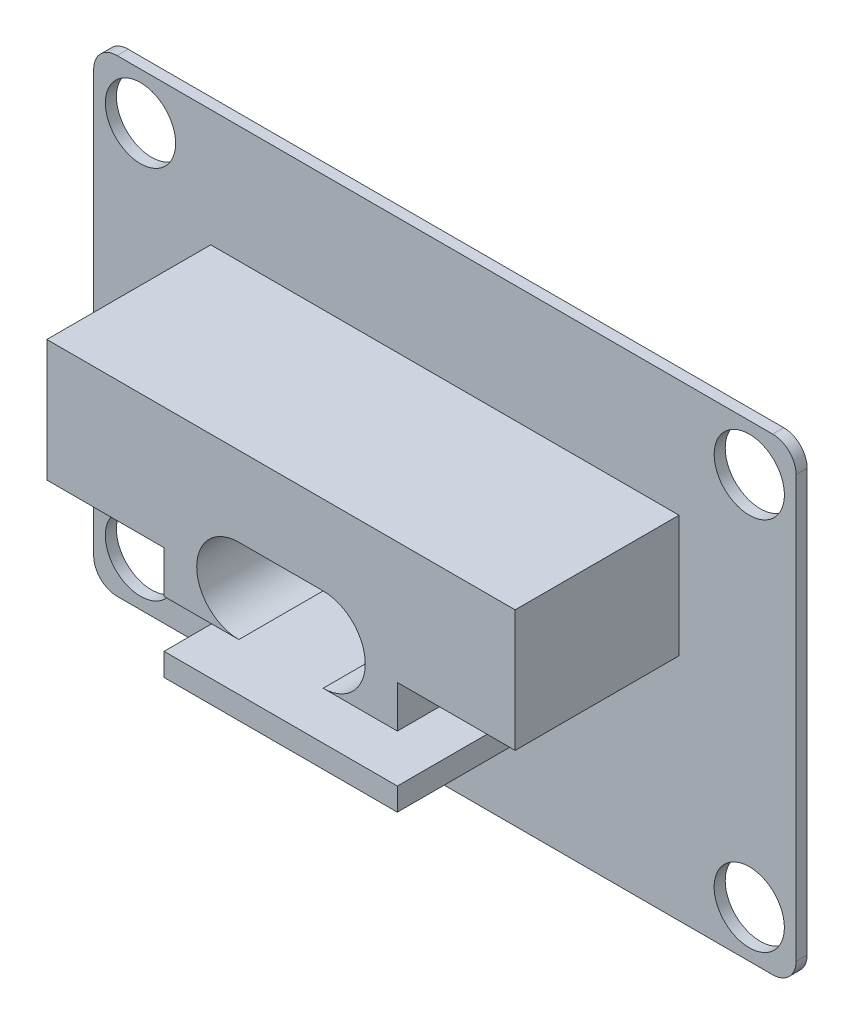
SolidWorks part; units mm, degrees
note: The reader was unsure of these and kept them because the rebuilt part matched: shared geometry of "Sketch3<3>".
ref_plane "Front Plane" through (0, 0, 0) normal (0, 0, 1) x (1, 0, 0)
ref_plane "Top Plane" through (0, 0, 0) normal (0, 1, 0) x (1, 0, 0)
ref_plane "Right Plane" through (0, 0, 0) normal (1, 0, 0) x (0, 0, -1)
sketch "Sketch1" plane through (0, 0, 0) normal (0, 0, 1) x (1, 0, 0)
  line L0 (19.05, 50.8) -> (19.05, 0) construction
  line L1 (0, 0) -> (38.1, 0)
  line L2 (0, 0) -> (0, 25.4)
  line L3 (0, 25.4) -> (38.1, 25.4)
  line L4 (38.1, 0) -> (38.1, 25.4)
  line L5 (6.35, 19.05) -> (31.75, 19.05)
  line L6 (6.35, 19.05) -> (6.35, 6.35)
  line L7 (6.35, 6.35) -> (31.75, 6.35)
  line L8 (31.75, 19.05) -> (31.75, 6.35)
  line L9 (76.2, 12.7) -> (0, 12.7) construction
  line L10 (0, 12.7) -> (-5.0228, 12.7) construction
  point P14 (19.05, 25.4)
  point P17 (38.1, 12.7)
  dimension "D1" = 38.1
  dimension "D2" = 25.4
  dimension "D3" = 25.4
  dimension "D4" = 12.7
  dimension "D5" = 6.35
  dimension "D6" = 6.35
extrude "Boss-Extrude1" add sketch "Sketch1" along normal blind 0.6 contours L3 L4 L1 L2
sketch "Sketch2" plane through (0, 0, 0.6) normal (0, 0, 1) x (1, 0, 0)
  line L0 (0, 0) -> (0, 25.4) construction
  line L1 (31.75, 19.05) -> (6.35, 19.05)
  line L2 (31.75, 19.05) -> (31.75, 6.35)
  line L3 (31.75, 6.35) -> (6.35, 6.35)
  line L4 (6.35, 19.05) -> (6.35, 6.35)
  line L5 (0, 25.4) -> (38.1, 25.4) construction
  dimension "D1" = 6.35
  dimension "D2" = 6.35
  dimension "D3" = 25.4
  dimension "D4" = 12.7
extrude "Boss-Extrude2" add sketch "Sketch2" along normal blind 8.89
sketch "Sketch3" plane through (0, 0, 9.49) normal (0, 0, 1) x (1, 0, 0)
  line L6 (16.764, 12.446) -> (21.336, 12.446) construction
  line L7 (16.764, 14.732) -> (21.336, 14.732)
  line L8 (16.764, 10.16) -> (21.336, 10.16)
  line L10 (31.75, 6.35) -> (31.75, 19.05) construction
  line L15 (19.05, 19.05) -> (19.05, -49980.95) construction
  line L16 (31.75, 19.05) -> (6.35, 19.05) construction
  line L25 (16.764, 10.16) -> (12.7071, 10.16)
  line L26 (12.7071, 10.16) -> (12.7071, 12.446)
  line L27 (12.7071, 12.446) -> (6.35, 12.446)
  line L28 (6.35, 19.05) -> (6.35, 6.35) construction
  line L29 (6.35, 12.446) -> (6.35, 19.05)
  line L30 (6.35, 19.05) -> (31.75, 19.05)
  line L31 (31.75, 19.05) -> (31.75, 12.446)
  line L32 (31.75, 12.446) -> (25.3621, 12.446)
  line L33 (25.3621, 12.446) -> (25.3621, 10.16)
  line L34 (25.3621, 10.16) -> (16.764, 10.16)
  line L35 (12.7071, 6.35) -> (12.7071, 7.5792)
  line L36 (6.35, 6.35) -> (31.75, 6.35) construction
  line L37 (12.7071, 7.5792) -> (25.3621, 7.5792)
  line L38 (25.3621, 7.5792) -> (25.3621, 6.35)
  line L39 (25.3621, 6.35) -> (12.7071, 6.35)
  arc A0 (16.764, 14.732) -> (16.764, 10.16) centre (16.764, 12.446) ccw
  arc A1 (21.336, 10.16) -> (21.336, 14.732) centre (21.336, 12.446) ccw
  point P10 (19.05, 12.446)
  point P27 (19.05, 19.05)
  dimension "D7" = 4.572
  dimension "D8" = 12.7
extrude "Cut-Extrude1" cut sketch "Sketch3" against normal blind 25.4
extrude "Cut-Extrude2" cut sketch "Sketch3<3>" against normal blind 8.89
sketch "Sketch3<3>" plane through (0, 0, 9.49) normal (0, 0, 1) x (1, 0, 0) same geometry as "Sketch3"
sketch "Sketch5" plane through (0, 0, 0.6) normal (0, 0, 1) x (1, 0, 0)
  line L0 (0, 0) -> (0, 25.4) construction
  line L1 (0, 25.4) -> (38.1, 25.4) construction
  line L2 (19.05, 25.4) -> (19.05, -49974.6) construction
  line L3 (0, 12.7) -> (50000, 12.7) construction
  circle A0 centre (2.54, 22.86) radius 1.905
  circle A1 centre (35.56, 22.86) radius 1.905
  circle A2 centre (2.54, 2.54) radius 1.905
  circle A3 centre (35.56, 2.54) radius 1.905
  point P8 (19.05, 25.4)
  point P11 (0, 12.7)
  dimension "D1" = 2.54
  dimension "D2" = 2.54
extrude "Cut-Extrude4" cut sketch "Sketch5" against normal blind 5.08 contours A2 | A1 | A0 | A3
fillet "Fillet4" radius 1.27 4 edges at (38.1, 0, 0.3) (0, 0, 0.3) (0, 25.4, 0.3) (38.1, 25.4, 0.3)
